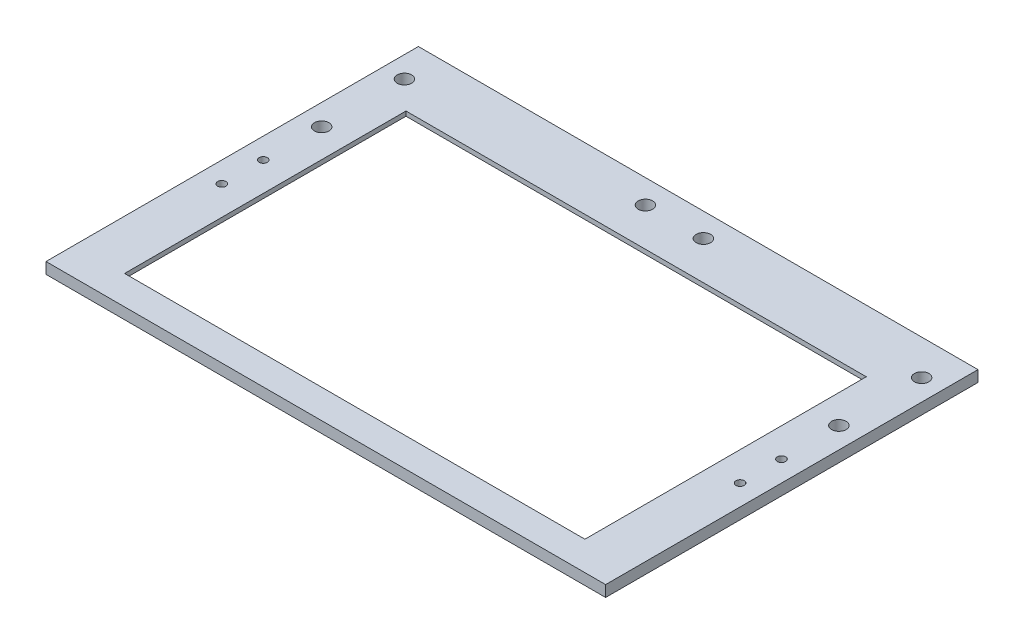
SolidWorks part; units mm, degrees
note: The reader was unsure of these and kept them because the rebuilt part matched: shared geometry of "Sketch1<5>".
ref_plane "Front Plane" through (0, 0, 0) normal (0, 0, 1) x (1, 0, 0)
ref_plane "Top Plane" through (0, 0, 0) normal (0, 1, 0) x (1, 0, 0)
ref_plane "Right Plane" through (0, 0, 0) normal (1, 0, 0) x (0, 0, -1)
sketch "Sketch1" plane through (0, 0, 0) normal (0, 1, 0) x (1, 0, 0)
  line L0 (135.25, 95) -> (135.25, -95)
  line L1 (-115.25, 75) -> (115.25, 75)
  line L2 (-115.25, 75) -> (-115.25, -75)
  line L3 (-115.25, -75) -> (115.25, -75)
  line L4 (115.25, 75) -> (115.25, -75)
  line L5 (-115.25, 75) -> (115.25, -75) construction
  line L6 (-115.25, -75) -> (115.25, 75) construction
  line L7 (-135.25, -95) -> (135.25, -95)
  line L8 (-135.25, 95) -> (-135.25, -95)
  line L10 (-111.25, -71) -> (111.25, -71)
  line L11 (111.25, 71) -> (111.25, -71)
  line L12 (-111.25, 71) -> (111.25, 71)
  line L13 (-111.25, 71) -> (-111.25, -71)
  line L14 (75, 83.5) -> (-75, 83.5) construction
  line L15 (-135.25, 95) -> (135.25, 95)
  line L18 (135.25, 95) -> (135.25, 72)
  line L19 (-141.2172, 0) -> (150.3085, 0) construction
  line L20 (-135.25, -95) -> (135.25, -95)
  line L21 (-135.25, -95) -> (-135.25, -110)
  line L22 (-135.25, -110) -> (135.25, -110)
  line L23 (135.25, -95) -> (135.25, -110)
  line L26 (0, -110) -> (0, 165.2145) construction
  line L27 (135.25, 95) -> (-135.25, 95)
  line L28 (135.25, 95) -> (135.25, 98)
  line L29 (135.25, 98) -> (-135.25, 98)
  line L30 (-135.25, 95) -> (-135.25, 98)
  line L31 (-135.25, 95) -> (135.25, 95) construction
  line L33 (-135.25, -85) -> (135.25, -85)
  line L35 (-115.25, 65) -> (115.25, 65)
  circle A2 centre (-14, 83.5) radius 3.5
  circle A3 centre (14, 83.5) radius 3.5
  circle A12 centre (-125, 78) radius 3.5
  circle A13 centre (-125, 38) radius 3.5
  circle A14 centre (125, 78) radius 3.5
  circle A15 centre (125, 38) radius 3.5
  circle A16 centre (-125.25, 10) radius 2
  circle A17 centre (-125.25, -10) radius 2
  circle A18 centre (125.25, -10) radius 2
  circle A19 centre (125.25, 10) radius 2
  point P0 (0, 0)
  point P20 (0, 83.5)
  point P21 (135.25, 83.5)
  dimension "D6" = 250
  dimension "D8" = 28
  dimension "D9" = 7
  dimension "D11" = 7
  dimension "D15" = 20
  dimension "D16" = 4
  dimension "D17" = 4
  dimension "D1" = 230.5
  dimension "D2" = 150
  dimension "D5" = 20
  dimension "D7" = 150
  dimension "D10" = 15
  dimension "D12" = 40
  dimension "D13" = 11.5
  dimension "D14" = 3
  dimension "D18" = 10
  dimension "D19" = 10
  dimension "D20" = 10
  dimension "D3" = 20
  dimension "D4" = 4
extrude "Boss-Extrude1" add sketch "Sketch1" along normal blind 5.4
extrude "Cut-Extrude1" cut sketch "Sketch1<5>" along normal blind 3.2 contours L1 L4 L3 L2
sketch "Sketch1<5>" plane through (0, 0, 0) normal (0, 1, 0) x (1, 0, 0) same geometry as "Sketch1"
sketch "Sketch2" plane through (0, 3.2, 0) normal (0, -1, 0) x (1, 0, 0)
  line L1 (115.25, -75) -> (94.75, -75)
  line L2 (115.25, -75) -> (115.25, -65)
  line L3 (115.25, -65) -> (94.75, -65)
  line L4 (-115.25, 75) -> (-115.25, -75)
  line L5 (-115.25, -75) -> (115.25, -75)
  line L6 (115.25, -75) -> (115.25, 75)
  line L7 (115.25, 75) -> (-115.25, 75)
  line L8 (-115.25, 75) -> (-115.25, -75)
  line L9 (-115.25, -75) -> (115.25, -75)
  line L10 (115.25, -75) -> (115.25, 75)
  line L11 (115.25, 75) -> (-115.25, 75)
  line L13 (115.25, 75) -> (94.75, 75)
  line L14 (115.25, 75) -> (115.25, 70)
  line L17 (-115.25, 75) -> (-94.75, 75)
  line L18 (-115.25, 75) -> (-115.25, 70)
  line L21 (-115.25, -75) -> (-94.75, -75)
  line L22 (-115.25, -75) -> (-115.25, -65)
  line L23 (-115.25, -65) -> (94.75, -65)
  line L25 (111.25, 75) -> (111.25, -65)
  line L26 (-111.25, 75) -> (-111.25, -75)
  dimension "D2" = 10
  dimension "D3" = 4
  dimension "D4" = 4
  dimension "D1" = 0
